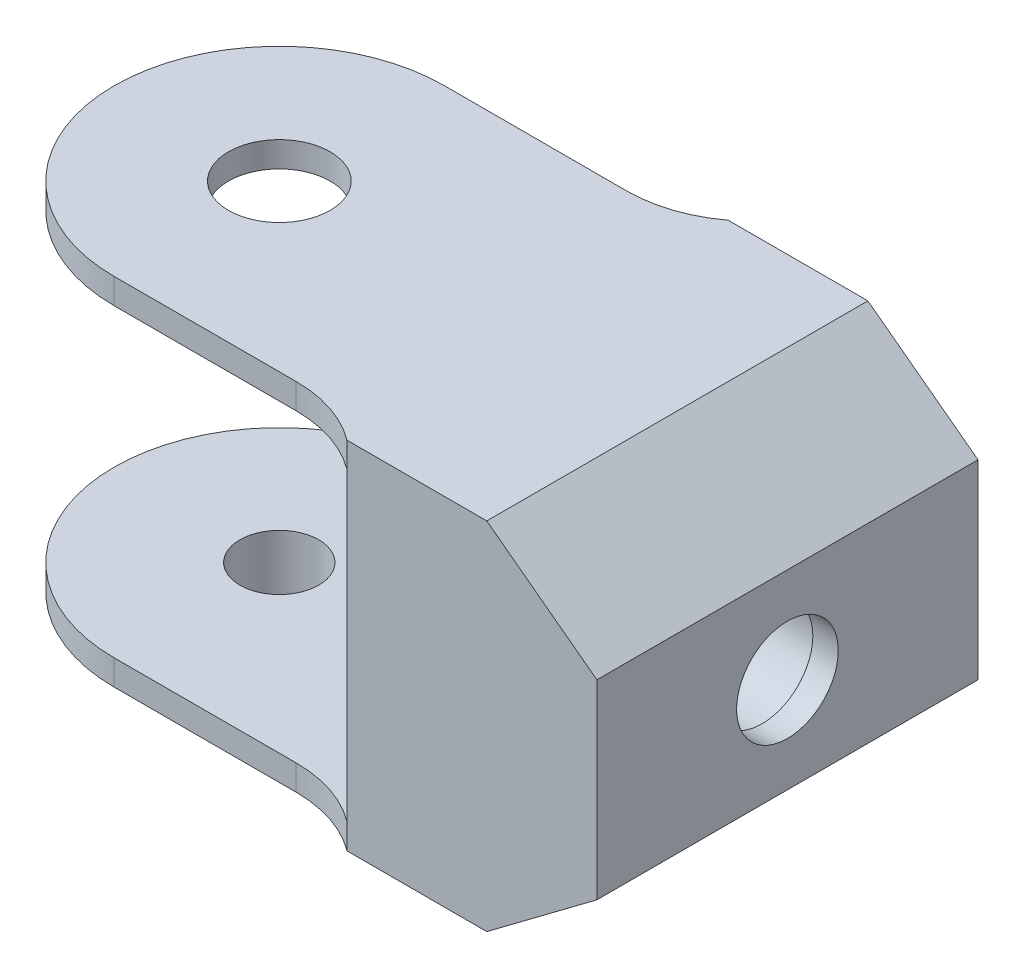
SolidWorks part; units mm, degrees
ref_plane "Front Plane" through (0, 0, 0) normal (0, 0, 1) x (1, 0, 0)
ref_plane "Top Plane" through (0, 0, 0) normal (0, 1, 0) x (1, 0, 0)
ref_plane "Right Plane" through (0, 0, 0) normal (1, 0, 0) x (0, 0, -1)
sketch "Sketch1" plane through (0, 0, 0) normal (0, 1, 0) x (1, 0, 0)
  line L1 (40, 13) -> (0, 13)
  line L2 (40, 13) -> (40, -13)
  line L3 (40, -13) -> (0, -13)
  arc A0 (0, 13) -> (0, -13) centre (0, 0) ccw
  dimension "D1" = 26
  dimension "D2" = 40
extrude "Boss-Extrude1" add sketch "Sketch1" along normal blind 2
sketch "Sketch2" plane through (0, 2, 0) normal (0, 1, 0) x (1, 0, 0)
  line L0 (0, -13) -> (40, -13) construction
  line L1 (40, 13) -> (38, 13)
  line L2 (40, 13) -> (40, -13)
  line L3 (40, -13) -> (38, -13)
  line L4 (38, 13) -> (38, -13)
  dimension "D1" = 2
extrude "Boss-Extrude2" add sketch "Sketch2" along normal blind 24
sketch "Sketch3" plane through (0, 26, 0) normal (0, 1, 0) x (1, 0, 0)
  line L1 (40, -13) -> (0, -13)
  line L2 (40, -13) -> (40, 13)
  line L3 (40, 13) -> (0, 13)
  arc A0 (0, 13) -> (0, -13) centre (0, 0) ccw
extrude "Boss-Extrude3" add sketch "Sketch3" along normal blind 2
sketch "Sketch4" plane through (40, 0, 0) normal (1, 0, 0) x (0, 0, -1)
  line L0 (-13, 28) -> (13, 28) construction
  line L1 (-13, 28) -> (-13, 0) construction
  circle A0 centre (0, 14) radius 4
  point P5 (0, 28)
  point P8 (-13, 14)
  dimension "D1" = 8
extrude "Cut-Extrude1" cut sketch "Sketch4" against normal blind 2
sketch "Sketch5" plane through (0, 0, 13) normal (0, 0, 1) x (1, 0, 0)
  line L0 (38, 5) -> (34, 2)
  line L9 (34, 2) -> (31.3333, 0)
  line L10 (0, 0) -> (40, 0) construction
  line L11 (31.3333, 0) -> (31.3333, 2)
  line L12 (0, 2) -> (38, 2) construction
  line L13 (31.3333, 2) -> (40, 8.5)
  line L14 (40, 28) -> (40, 0) construction
  line L15 (40, 8.5) -> (40, 6.5)
  line L16 (40, 6.5) -> (38, 5)
  line L17 (40, 14) -> (19.1052, 14) construction
  line L18 (40, 21.5) -> (38, 23)
  line L19 (40, 19.5) -> (40, 21.5)
  line L20 (31.3333, 26) -> (40, 19.5)
  line L21 (31.3333, 28) -> (31.3333, 26)
  line L22 (34, 26) -> (31.3333, 28)
  line L23 (38, 23) -> (34, 26)
  dimension "D5" = 2
extrude "Boss-Extrude4" add sketch "Sketch5" against normal up to surface (26 mm away) up to face at (19.5, 14, -13)
sketch "Sketch6" plane through (0, 0, 13) normal (0, 0, 1) x (1, 0, 0)
  line L0 (38, 5) -> (31.3333, 0)
  line L1 (0, 0) -> (40, 0) construction
  line L2 (31.3333, 0) -> (40, 0)
  line L3 (40, 0) -> (40, 6.5)
  line L4 (40, 28) -> (40, 0) construction
  line L5 (40, 6.5) -> (38, 5)
  line L6 (34, 2) -> (38, 5) construction
  line L7 (40, 14) -> (25.7632, 14) construction
  line L8 (40, 28) -> (40, 21.5)
  line L9 (31.3333, 28) -> (40, 28)
  line L10 (38, 23) -> (31.3333, 28)
  line L11 (40, 21.5) -> (38, 23)
extrude "Cut-Extrude2" cut sketch "Sketch6" against normal up to surface (26 mm away) up to face at (36.6667, 3, -13)
sketch "Sketch7" plane through (0, 0, 13) normal (0, 0, 1) x (1, 0, 0)
  line L0 (40, 21.5) -> (31.3333, 28)
  line L1 (31.3333, 28) -> (20.3333, 28)
  line L2 (0, 28) -> (31.3333, 28) construction
  line L3 (20.3333, 28) -> (20.3333, 0)
  line L4 (0, 0) -> (31.3333, 0) construction
  line L5 (20.3333, 0) -> (31.3333, 0)
  line L6 (31.3333, 0) -> (40, 6.5)
  line L7 (40, 6.5) -> (40, 21.5)
  dimension "D1" = 11
extrude "Boss-Extrude5" add sketch "Sketch7" along normal blind 2
ref_plane "Plane1" through (0, 0, 0) normal (0, 0, 1) x (1, 0, 0)
mirror "Mirror1" about plane through (0, 0, 0) normal (0, 0, 1) of "Boss-Extrude5"
sketch "Sketch8" plane through (38, 0, 0) normal (-1, 0, 0) x (0, 0, 1)
  circle A0 centre (0, 14) radius 4.4884
  circle A1 centre (0, 14) radius 7.515
extrude "Boss-Extrude6" add sketch "Sketch8" along normal blind 4
sketch "Sketch9" plane through (0, 0, 0) normal (0, -1, 0) x (1, 0, 0)
  circle A0 centre (0, 0) radius 3.1
  dimension "D1" = 6.2
extrude "Cut-Extrude3" cut sketch "Sketch9" against normal blind 10
sketch "Sketch10" plane through (0, 28, 0) normal (0, 1, 0) x (1, 0, 0)
  circle A0 centre (0, 0) radius 4
  dimension "D1" = 8
extrude "Cut-Extrude4" cut sketch "Sketch10" against normal blind 10
sketch "Sketch11" plane through (0, 0, 0) normal (0, -1, 0) x (1, 0, 0)
  circle A0 centre (0, 0) radius 3.1
  circle A1 centre (0, 0) radius 4
  dimension "D1" = 8
  dimension "D2" = 6.2
extrude "Boss-Extrude7" add sketch "Sketch11" along normal blind 7
sketch "Sketch12" plane through (0, -7, 0) normal (0, -1, 0) x (1, 0, 0)
  circle A0 centre (0, 0) radius 4
extrude "Boss-Extrude8" add sketch "Sketch12" along normal blind 1
sketch "Sketch13" plane through (0, 0, 15) normal (0, 0, 1) x (1, 0, 0)
  line L0 (20.3333, 28) -> (20.3333, 0) construction
  line L1 (25.3333, 19) -> (30.3333, 19)
  line L2 (25.3333, 19) -> (25.3333, 9)
  line L3 (25.3333, 9) -> (30.3333, 9)
  line L4 (30.3333, 19) -> (30.3333, 9)
  line L5 (40, 6.5) -> (40, 21.5) construction
  point P8 (40, 14)
  point P9 (30.3333, 14)
  dimension "D1" = 10
  dimension "D2" = 5
  dimension "D3" = 5
extrude "Cut-Extrude5" cut sketch "Sketch13" against normal blind 10
sketch "Sketch14" plane through (0, 0, -15) normal (0, 0, -1) x (-1, 0, 0)
  line L1 (-30.3333, 19) -> (-25.3333, 19)
  line L2 (-30.3333, 19) -> (-30.3333, 9)
  line L3 (-30.3333, 9) -> (-25.3333, 9)
  line L4 (-25.3333, 19) -> (-25.3333, 9)
extrude "Cut-Extrude6" cut sketch "Sketch14" against normal blind 4
sketch "Sketch15" plane through (0, 0, 15) normal (0, 0, 1) x (1, 0, 0)
  line L1 (25.3333, 19) -> (30.3333, 19)
  line L2 (25.3333, 19) -> (25.3333, 9)
  line L3 (25.3333, 9) -> (30.3333, 9)
  line L4 (30.3333, 19) -> (30.3333, 9)
extrude "Boss-Extrude9" add sketch "Sketch15" against normal blind 2
sketch "Sketch16" plane through (0, 0, -15) normal (0, 0, -1) x (-1, 0, 0)
  line L1 (-25.3333, 19) -> (-30.3333, 19)
  line L2 (-25.3333, 19) -> (-25.3333, 21)
  line L3 (-25.3333, 21) -> (-30.3333, 21)
  line L4 (-30.3333, 19) -> (-30.3333, 21)
  line L5 (-30.3333, 9) -> (-25.3333, 9)
  line L6 (-30.3333, 9) -> (-30.3333, 7)
  line L7 (-30.3333, 7) -> (-25.3333, 7)
  line L8 (-25.3333, 9) -> (-25.3333, 7)
  dimension "D1" = 2
  dimension "2" = 2
extrude "Boss-Extrude10" add sketch "Sketch16" along normal blind 2
sketch "Sketch17" plane through (0, 0, -17) normal (0, 0, -1) x (-1, 0, 0)
  line L1 (-30.3333, 21) -> (-25.3333, 21)
  line L2 (-30.3333, 21) -> (-30.3333, 7)
  line L3 (-30.3333, 7) -> (-25.3333, 7)
  line L4 (-25.3333, 21) -> (-25.3333, 7)
extrude "Boss-Extrude11" add sketch "Sketch17" along normal blind 2
fillet "Fillet1" radius 10 2 edges at (20.3333, 27, -13) (20.3333, 27, 13)
